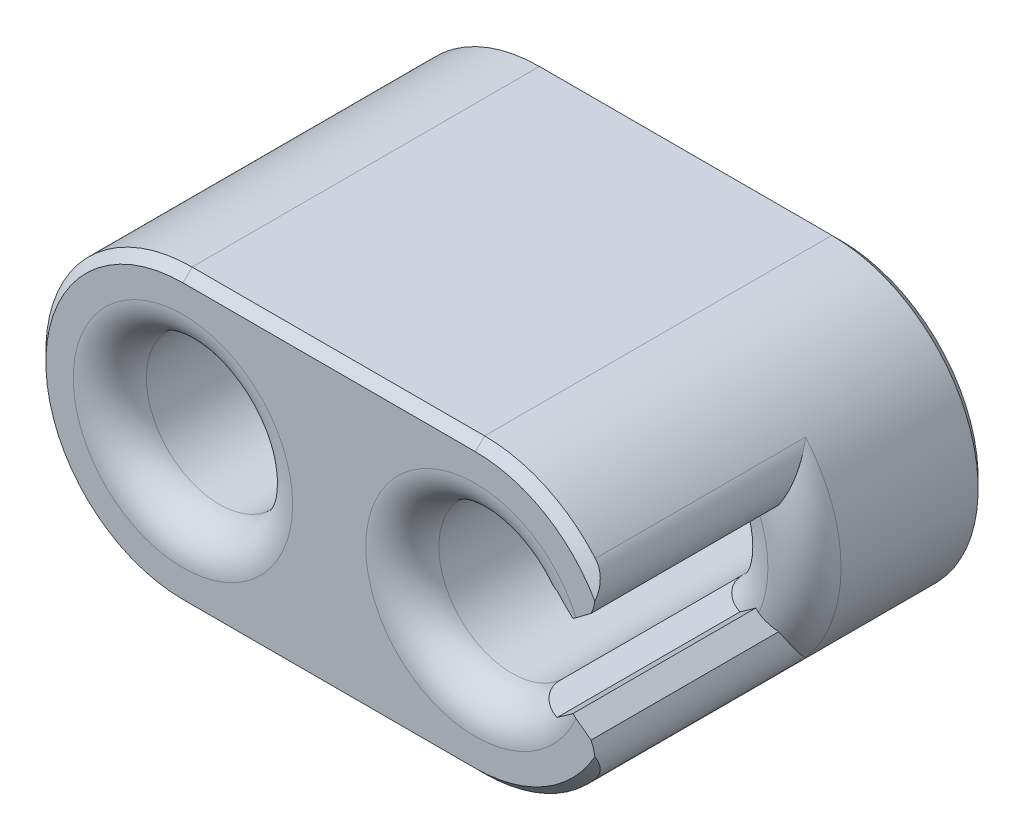
SolidWorks part; units mm, degrees
ref_plane "Front Plane" through (0, 0, 0) normal (0, 0, 1) x (1, 0, 0)
ref_plane "Top Plane" through (0, 0, 0) normal (0, 1, 0) x (1, 0, 0)
ref_plane "Right Plane" through (0, 0, 0) normal (1, 0, 0) x (0, 0, -1)
sketch "Sketch1" plane through (0, 0, 0) normal (0, 0, 1) x (1, 0, 0)
  line L0 (0, 4) -> (8, 4)
  line L1 (0, -4) -> (8, -4)
  circle A0 centre (0, 0) radius 2
  circle A1 centre (0, 0) radius 4
  circle A2 centre (8, 0) radius 4
  circle A3 centre (8, 0) radius 2
  point P5 (13.625, 0)
  point P10 (14.9194, -0.894)
  point P14 (8.8418, 0)
  point P15 (0, 0)
  point P18 (0, 0)
  point P19 (13.625, 0)
  point P20 (13.1302, 0)
  dimension "D1" = 4
  dimension "D2" = 2
extrude "Boss-Extrude1" add sketch "Sketch1" against normal blind 10
ref_plane "Plane1" through (12, 0, 0) normal (1, 0, 0) x (0, 0, -1)
sketch "Sketch3" plane through (12, 0, 0) normal (0, 0, -1) x (-1, 0, 0)
  line L50 (1.8386, 1.5) -> (1.3386, 1.125)
  line L51 (1.3386, 1.125) -> (0.8386, 1.5)
  line L52 (0.8386, 1.5) -> (1.8386, 1.5)
  line L53 (2.6771, 1.5) -> (0, 1.5)
  line L54 (0, 1.5) -> (0, -1.5)
  line L55 (0, -1.5) -> (2.6771, -1.5)
  line L56 (2.6771, -1.5) -> (2.6771, 1.5)
  line L57 (1.8386, -1.5) -> (1.3386, -1.125)
  line L58 (1.3386, -1.125) -> (0.8386, -1.5)
  line L59 (4.5562, 0) -> (-3.7444, 0) construction
  line L60 (1.3386, 1.5) -> (1.3386, -1.5) construction
  circle A0 centre (4, 0) radius 2 construction
  arc A1 (4, 4) -> (4, -4) centre (4, 0) ccw construction
  point P13 (0, 0)
  point P17 (0, 0)
  point P20 (0, 0)
  point P23 (1.3386, 1.125)
  arc M50 (4, -4) -> (4, 4) centre (4, 0) cw
  circle M54 centre (4, 0) radius 2
  dimension "D1" = 3
  dimension "D2" = 2.25
  dimension "D3" = 1
fillet "Fillet1" radius 1 4 edges at (2, 0, -10) (2, 0, 0) (10, 0, -10) (10, 0, 0)
chamfer "Chamfer1" distance 0.25 angle 45 8 edges at (4, 4, 0) (4, 4, -10) (-4, 0, 0) (-4, 0, -10) (12, 0, 0) (12, 0, -10) (4, -4, 0) (4, -4, -10)
extrude "Cut-Extrude2" cut sketch "Sketch3" along normal blind 5 contours L57 L58 L55 L53 L51 L50 M50 M54
fillet "Fillet2" radius 1 2 edges at (12, 0, -5) (10, 0, -5)
fillet "Fillet3" radius 1 2 edges at (11.7081, -1.5, -3.125) (11.7081, 1.5, -3.125)
